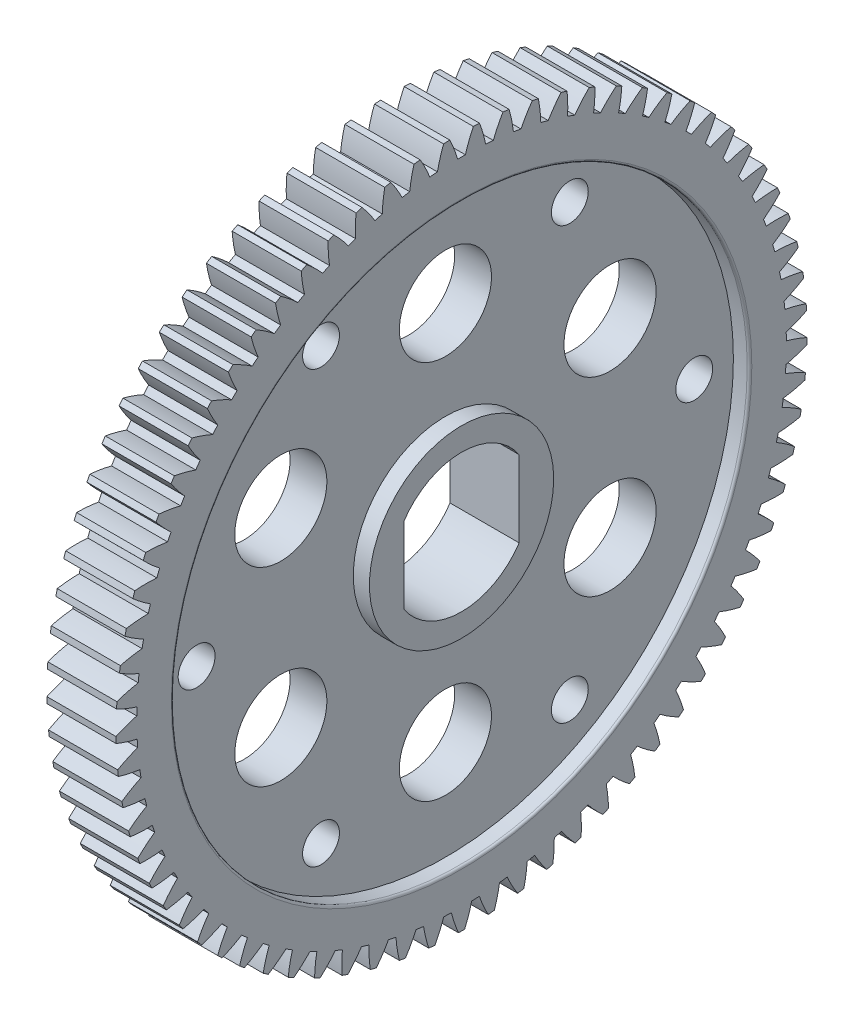
SolidWorks part; units mm, degrees
ref_plane "Plane1" through (0, 0, 0) normal (0, 0, 1) x (1, 0, 0)
ref_plane "Plane2" through (0, 0, 0) normal (0, 1, 0) x (1, 0, 0)
ref_plane "Plane3" through (0, 0, 0) normal (1, 0, 0) x (0, 0, -1)
other "Configuration Table"
sketch "HoldingSke" plane through (0, 0, 0) normal (0, 1, 0) x (1, 0, 0)
  line L0 (0, 0) -> (0.1462, -0.4782)
  line L1 (-15, 0) -> (100, 0) construction
  line L2 (0, 0) -> (-2.1039, 2.3779)
  line L3 (0, 0) -> (-11.863, 4.5341)
  line L4 (0, 0) -> (2.5249, 8.2586)
  line L5 (0, 0) -> (-46.8476, -17.4728)
  line L6 (0, 0) -> (-12.4344, -8.3896)
  line L7 (-2.1039, 2.3779) -> (8.6586, 51.2059)
  line L8 (-76.2, 54.61) -> (-76.1, 54.61)
  line L9 (-71.009, 38.7566) -> (-53.1078, 45.2721)
  line L10 (-76.2, 71.12) -> (104.1128, 71.12)
  line L11 (0, 0) -> (-15, 0)
  line L12 (-76.2, 101.6) -> (-76.133, 101.6)
  line L13 (24.9733, 27.94) -> (52.9518, 28.4284)
  line L14 (24.9733, 27.94) -> (24.9743, 27.94)
  line L15 (24.9733, 27.94) -> (100.4006, 29.5858)
  line L16 (-63.627, -2) -> (-12.827, -2)
  circle A0 centre (0, 0) radius 0.4
  circle A1 centre (0, 0) radius 37.5
  circle A2 centre (0, 0) radius 37.5
  circle A3 centre (0, 0) radius 0.4
  dimension "Num_teeth" = 73
  dimension "Pitch_radius" = 180.3128
  dimension "Width" = 15
  dimension "Thickness" = 15
sketch "BasProSke" plane through (0, 0, 0) normal (0, 1, 0) x (1, 0, 0)
  line L0 (-10, 0) -> (60, 0) construction
  line L1 (0, 0) -> (0, 75)
  line L2 (0, 0) -> (15, 0)
  line L3 (15, 0) -> (15, 75)
  line L4 (15, 75) -> (0, 75)
  dimension "Thickness" = 15
  dimension "Diameter" = 150
revolve "Base-Revolve" add sketch "BasProSke" angle 360 about L0
sketch "TooCutSke" plane through (0, 0, 0) normal (1, 0, 0) x (0, 0, -1)
  line L1 (0, 0) -> (0, 107) construction
  line L2 (0, 0) -> (-1.6879, 72.9805) construction
  line L3 (0, 0) -> (-6.28, 145.8359) construction
  line L4 (-1.6879, 72.9805) -> (-3.14, 72.918) construction
  arc A0 (0.8318, 70.4941) -> (-0.8318, 70.4941) centre (0, 0) ccw
  arc A1 (2.5674, 74.9815) -> (-2.5674, 74.9815) centre (0, 0) ccw
  circle A2 centre (0, 0) radius 73 construction
  circle A3 centre (0, 0) radius 68.5976 construction
  arc A4 (-0.8318, 70.4941) -> (-2.5674, 74.9815) centre (-28.8409, 62.2401) ccw
  arc A5 (2.5674, 74.9815) -> (0.8318, 70.4941) centre (28.8409, 62.2401) ccw
extrude "ToothCut" cut sketch "TooCutSke" along normal through all
fillet "Breaks" [suppressed] radius 0.04 tangent propagation no
fillet "RootFillets" [suppressed] radius 0.501
pattern_circular "TeethCuts" count 73 every 4.932 about axis through (-10, 0, 0) along (1, 0, 0) of "ToothCut", "RootFillets", "Breaks"
sketch "HubNeaOneSke" plane through (0, 0, 0) normal (-1, 0, 0) x (0, 0, 1)
  circle A0 centre (0, 0) radius 37.5
  dimension "Diameter" = 75
extrude "HubNearOne" [suppressed] add sketch "HubNeaOneSke" along normal blind 35.0001
sketch "HubNeaBotSke" plane through (0, 0, 0) normal (-1, 0, 0) x (0, 0, 1)
  circle A0 centre (0, 0) radius 37.5
  dimension "Diameter" = 75
extrude "HubNearBoth" [suppressed] add sketch "HubNeaBotSke" along normal blind 17.5
ref_plane "FarPln" through (15, 0, 0) normal (1, 0, 0) x (0, 0, -1)
sketch "HubFarSke" plane through (15, 0, 0) normal (1, 0, 0) x (0, 0, -1)
  circle A0 centre (0, 0) radius 37.5
  dimension "Diameter" = 75
extrude "HubFar" [suppressed] add sketch "HubFarSke" along normal blind 17.5
sketch "BorSke" plane through (0, 0, 0) normal (1, 0, 0) x (0, 0, -1)
  circle A0 centre (0, 0) radius 0.4
  dimension "Diameter" = 0.8
extrude "Bore" cut sketch "BorSke" along normal mid plane 100.0001
sketch "KeySke" plane through (0, 0, 0) normal (1, 0, 0) x (0, 0, -1)
  line L0 (-0.05, 0) -> (-0.05, 0.5)
  line L1 (-0.05, 0.5) -> (0.05, 0.5)
  line L2 (0.05, 0.5) -> (0.05, 0)
  line L3 (0, 0) -> (0, 34) construction
  line L4 (-0.05, 0) -> (0.05, 0)
extrude "Keyway" [suppressed] cut sketch "KeySke" along normal mid plane 100.0001
pattern_circular "Keyway2" [suppressed] count 2 every 90 about axis through (-10, 0, 0) along (1, 0, 0)
sketch "Sketch1" plane through (15, 0, 0) normal (1, 0, 0) x (0, 0, -1)
  circle A0 centre (0, -0.4) radius 62.5
  circle A1 centre (0, 0) radius 0.4 construction
  dimension "D1" = 125
extrude "Cut-Extrude1" cut sketch "Sketch1" against normal blind 3.5
extrude "Cut-Extrude2" cut sketch "Sketch1<2>" along normal blind 3.5 from surface starting at face at (0, 0, -0.4)
sketch "Sketch1<2>" plane through (15, 0, 0) normal (1, 0, 0) x (0, 0, -1) same geometry as "Sketch1"
fillet "Fillet1" radius 0.5 1 edges at (15, -0.4, -62.5)
fillet "Fillet2" radius 0.5 1 edges at (0, -0.4, -62.5)
sketch "Sketch2" plane through (11.5, 0, 0) normal (1, 0, 0) x (0, 0, -1)
  circle A0 centre (0, 0) radius 20
  dimension "D1" = 40
extrude "Boss-Extrude1" add sketch "Sketch2" along normal blind 3.5 and the other way blind 11.5
sketch "Sketch3" plane through (15, 0, 0) normal (1, 0, 0) x (0, 0, -1)
  line L0 (-12.5, 8.2916) -> (-12.5, -8.2916)
  line L1 (12.5, 8.2916) -> (12.5, -8.2916)
  line L2 (0, 0) -> (0, 12.7673) construction
  arc A0 (-12.5, -8.2916) -> (12.5, -8.2916) centre (0, 0) ccw
  arc A1 (12.5, 8.2916) -> (-12.5, 8.2916) centre (0, 0) ccw
  dimension "D1" = 30
  dimension "D2" = 25
extrude "Cut-Extrude3" cut sketch "Sketch3" against normal up to next
sketch "Sketch4" plane through (11.5, 0, 0) normal (1, 0, 0) x (0, 0, -1)
  line L0 (27, 46.7654) -> (0, 0) construction
  line L1 (0, 0) -> (49.1983, 0) construction
  circle A0 centre (0, 0) radius 41.25 construction
  circle A1 centre (0, 41.25) radius 10
  circle A2 centre (0, 0) radius 54 construction
  circle A3 centre (27, 46.7654) radius 4
  dimension "D1" = 82.5
  dimension "D2" = 20
  dimension "D3" = 108
  dimension "D4" = 8
  dimension "D5" = 60
extrude "Cut-Extrude4" cut sketch "Sketch4" against normal up to next
pattern_circular "CirPattern1" count 6 over 360 about axis through (0, 0, 0) along (1, 0, 0) of "Cut-Extrude4" reverse direction yes
equation "' \"Module@HoldingSke\" = 6.35"
equation "' \"Num_teeth@HoldingSke\" = 12"
equation "' \"Ap@HoldingSke\" =  20"
equation "' \"Ap@HoldingSke\" = 20"
equation "' \"Width@HoldingSke\" = 0.5 * 25.4"
equation "' \"Hub_dia@HoldingSke\"= 1 * 25.4"
equation "' \"Hub_dia@HoldingSke\" = 1 * 25.4"
equation "' \"Overall_len@HoldingSke\" = 1.0 * 25.4"
equation "' \"Bore@HoldingSke\" = 0.75 * 25.4"
equation "' \"T_dim@HoldingSke\" = 0.1 * 25.4"
equation "' \"Width@KeySke\" = 0.25 * 25.4"
equation "' \"Show_teeth@HoldingSke\" = 13"
equation "' \"Backlash@HoldingSke\" = 0.009 * 25.4"
equation "' \"Addendum_fac@HoldingSke\" = 1.0"
equation "' \"Dedendum_fac@HoldingSke\" = 1.25"
equation "' \"Dedendum_add@HoldingSke\" = 0.00005 * 25.4"
equation "' \"Clearance_fac@HoldingSke\" = 0.25"
equation "\"Pitch@HoldingSke\" = 1 / \"Module@HoldingSke\""
equation "\"Overcut_dia@TooCutSke\" = (\"Num_teeth@HoldingSke\" + 2 * \"Addendum_fac@HoldingSke\") / \"Pitch@HoldingSke\" + 0.002 * 25.4"
equation "\"Pitch_dia@TooCutSke\" = \"Num_teeth@HoldingSke\" / \"Pitch@HoldingSke\""
equation "\"Base_dia@TooCutSke\" = \"Num_teeth@HoldingSke\" / \"Pitch@HoldingSke\" * cos((\"Ap@HoldingSke\"  * 3.14159265 / 180))"
equation "\"Root_dia@TooCutSke\" = (\"Num_teeth@HoldingSke\" + 2) / \"Pitch@HoldingSke\" - 2 * (\"Addendum_fac@HoldingSke\" + \"Dedendum_fac@HoldingSke\") / \"Pitch@HoldingSke\" - \"Dedendum_add@HoldingSke\" * 2"
equation "\"Half_ang@TooCutSke\" = 180 / \"Num_teeth@HoldingSke\""
equation "\"Half_CT@TooCutSke\" = \"Num_teeth@HoldingSke\" / \"Pitch@HoldingSke\" * sin((3.14159265 / 2 / \"Num_teeth@HoldingSke\")) / 2 - 7 * \"Backlash@HoldingSke\" / 4"
equation "\"Flank_rad@TooCutSke\" = \"Num_teeth@HoldingSke\" / \"Pitch@HoldingSke\" / 5"
equation "\"Radius@RootFillets\" = \"Clearance_fac@HoldingSke\" / \"Pitch@HoldingSke\" + \"Dedendum_add@HoldingSke\""
equation "\"Break_rad@Breaks\" = 0.02 / \"Pitch@HoldingSke\""
equation "\"Thickness@HoldingSke\" = \"Width@HoldingSke\""
equation "\"OAL@HoldingSke\" = \"Thickness@HoldingSke\""
equation "\"MHD@HoldingSke\" = (\"Num_teeth@HoldingSke\" + 2) / \"Pitch@HoldingSke\" - 2 * (\"Addendum_fac@HoldingSke\" + \"Dedendum_fac@HoldingSke\")  / \"Pitch@HoldingSke\" - \"Dedendum_add@HoldingSke\" * 2"
equation "\"MBD@HoldingSke\" = (\"Num_teeth@HoldingSke\" + 2) / \"Pitch@HoldingSke\" - 2 * (\"Addendum_fac@HoldingSke\" + \"Dedendum_fac@HoldingSke\")  / \"Pitch@HoldingSke\" - \"Dedendum_add@HoldingSke\" * 2 - 0.002 * 25.4"
equation "\"MHD@HoldingSke\" = ((sgn( \"MHD@HoldingSke\" - \"Hub_dia@HoldingSke\" )-1)*( \"MHD@HoldingSke\" - \"Hub_dia@HoldingSke\" ))/-2+ \"Hub_dia@HoldingSke\""
equation "\"MBD@HoldingSke\" = ((sgn( \"MBD@HoldingSke\" - \"Bore@HoldingSke\" )-1)*( \"MBD@HoldingSke\" - \"Bore@HoldingSke\" ))/-2+ \"Bore@HoldingSke\""
equation "\"OAL@HoldingSke\" = ((sgn( \"OAL@HoldingSke\" - \"Overall_len@HoldingSke\" )+1)*( \"OAL@HoldingSke\" - \"Overall_len@HoldingSke\" ))/2 + \"Overall_len@HoldingSke\" + 0.000002 * 25.4"
equation "\"Num_teeth@TeethCuts\" = int( \"Show_teeth@HoldingSke\" ) + 1"
equation "\"Num_teeth@TeethCuts\" = ((sgn( \"Num_teeth@TeethCuts\" - \"Num_teeth@HoldingSke\" )-1)*( \"Num_teeth@TeethCuts\" - \"Num_teeth@HoldingSke\" ))/-2+ \"Num_teeth@HoldingSke\""
equation "\"Num_teeth@TeethCuts\" = ((sgn( \"Num_teeth@TeethCuts\" - 2.0)+1)*( \"Num_teeth@TeethCuts\" - 2.0))/2 +2.0"
equation "\"Angle@TeethCuts\" = 360.0 / \"Num_teeth@HoldingSke\""
equation "\"Diameter@BasProSke\" = (\"Num_teeth@HoldingSke\" + 2 * \"Addendum_fac@HoldingSke\") / \"Pitch@HoldingSke\""
equation "\"Thickness@BasProSke\"  = \"Thickness@HoldingSke\""
equation "' \"Fillet_rad@BasProSke\" =  \"Thickness@HoldingSke\" * 0.05"
equation "' \"Fillet_rad@BasProSke\" = \"Thickness@HoldingSke\" * 0.05"
equation "\"MHD@HoldingSke\" = ((sgn( \"MHD@HoldingSke\" - \"Root_dia@TooCutSke\" )-1)*( \"MHD@HoldingSke\" - \"Root_dia@TooCutSke\" ))/-2+ \"Root_dia@TooCutSke\""
equation "\"Diameter@HubNeaOneSke\" = \"MHD@HoldingSke\""
equation "\"Length@HubNearOne\" = \"OAL@HoldingSke\" - \"Thickness@BasProSke\""
equation "\"Diameter@HubNeaBotSke\" = \"MHD@HoldingSke\""
equation "\"Length@HubNearBoth\" = ( \"OAL@HoldingSke\" - \"Thickness@BasProSke\" ) / 2.0"
equation "\"Thickness@FarPln\" = \"Thickness@BasProSke\""
equation "\"Diameter@HubFarSke\" = \"MHD@HoldingSke\""
equation "\"Length@HubFar\" = ( \"OAL@HoldingSke\" - \"Thickness@BasProSke\" ) / 2.0"
equation "\"Diameter@BorSke\" = \"MBD@HoldingSke\""
equation "\"D1@Bore\" = \"OAL@HoldingSke\" * 2.0"
equation "\"D1@Keyway\" = \"OAL@HoldingSke\" * 2.0"
equation "\"Offset@KeySke\" = \"T_dim@HoldingSke\" + \"MBD@HoldingSke\" / 2.0"
